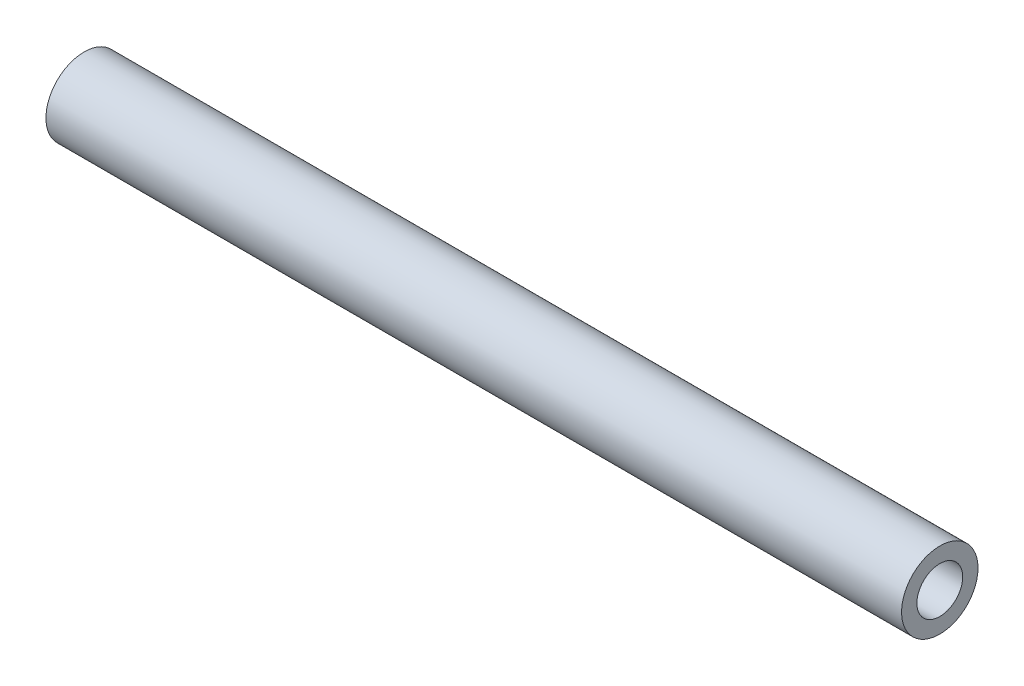
SolidWorks part; units mm, degrees
material "Thornel Mat VMA"
ref_plane "Front Plane" through (0, 0, 0) normal (0, 0, 1) x (1, 0, 0)
ref_plane "Top Plane" through (0, 0, 0) normal (0, 1, 0) x (1, 0, 0)
ref_plane "Right Plane" through (0, 0, 0) normal (1, 0, 0) x (0, 0, -1)
sketch "Sketch1" plane through (0, 0, 0) normal (1, 0, 0) x (0, 0, -1)
  circle A0 centre (0, 0) radius 4.7625
  circle A1 centre (0, 0) radius 7.9375
  dimension "D1" = 9.525
  dimension "D2" = 15.875
extrude "Boss-Extrude1" add sketch "Sketch1" along normal mid plane 177.8
